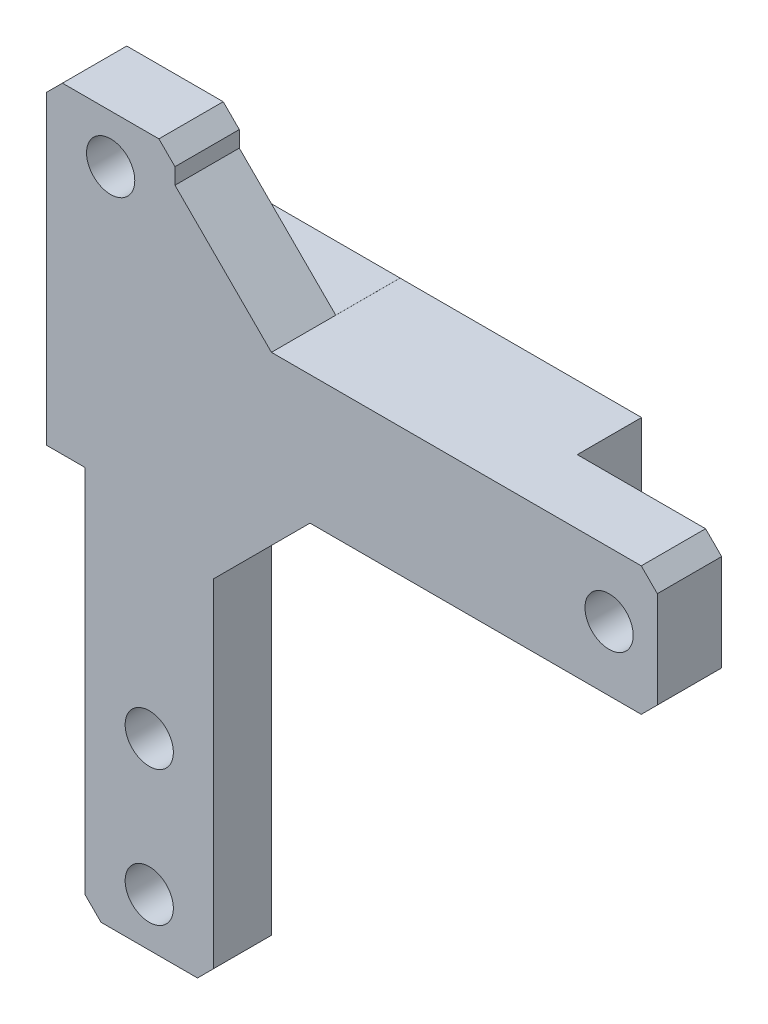
SolidWorks part; units mm, degrees
ref_plane "前视基准面" through (0, 0, 0) normal (0, 0, 1) x (1, 0, 0)
ref_plane "上视基准面" through (0, 0, 0) normal (0, 1, 0) x (1, 0, 0)
ref_plane "右视基准面" through (0, 0, 0) normal (1, 0, 0) x (0, 0, -1)
other "Configuration Table"
sketch "草图1" plane through (0, 0, 0) normal (0, 0, 1) x (1, 0, 0)
  line L0 (-4.3, -2.5) -> (9.5, -2.5)
  line L1 (-5.5, 1.5) -> (9.5, 1.5)
  line L4 (9.5, 1.5) -> (9.5, -2.5)
  line L8 (-9.5, 1.5) -> (-9.5, 5.5)
  line L9 (-9.5, 5.5) -> (-5.5, 5.5)
  line L11 (-5.5, 1.5) -> (-5.5, 5.5)
  line L12 (-9.5, 1.5) -> (-9.5, -4.5)
  line L13 (-8.3, -4.5) -> (-8.3, -16.5)
  line L14 (-8.3, -16.5) -> (-4.3, -16.5)
  line L15 (-4.3, -16.5) -> (-4.3, -2.5)
  line L16 (-9.5, -4.5) -> (-8.3, -4.5)
  circle A0 centre (8, -0.5) radius 0.75
  circle A1 centre (-7.5, 4) radius 0.75
  circle A2 centre (-6.3, -15) radius 0.75
  circle A3 centre (-6.3, -10.8) radius 0.75
  point P0 (0, 0)
  dimension "D16" = 1.5
  dimension "D2" = 6
  dimension "D4" = 2
  dimension "D5" = 1.5
  dimension "D6" = 10
  dimension "D7" = 4
  dimension "D9" = 2
  dimension "D10" = 1.5
  dimension "D11" = 4
  dimension "D12" = 4
  dimension "D13" = 2
  dimension "D14" = 19
  dimension "D17" = 4.2
  dimension "D18" = 1.5
  dimension "D19" = 2
extrude "凸台-拉伸1" add sketch "草图1" along normal blind 4
sketch "草图2" plane through (0, 0, 0) normal (0, 0, 1) x (1, 0, 0)
  line L0 (-8.3, -4.8687) -> (-4.3, -4.8687)
  line L10 (9.5, -2.5) -> (9.5, 1.5)
  line L11 (9.5, 1.5) -> (-5.5, 1.5)
  line L12 (-5.5, 1.5) -> (-5.5, 5.5)
  line L13 (-5.5, 5.5) -> (-9.5, 5.5)
  line L14 (-9.5, 5.5) -> (-9.5, -4.5)
  line L15 (-9.5, -4.5) -> (-8.3, -4.5)
  line L16 (-8.3, -4.5) -> (-8.3, -16.5)
  line L17 (-8.3, -16.5) -> (-4.3, -16.5)
  line L18 (-4.3, -16.5) -> (-4.3, -2.5)
  line L19 (-4.3, -2.5) -> (9.5, -2.5)
  line L26 (-8.3, -4.8687) -> (-8.3, -16.5)
  line L27 (-8.3, -16.5) -> (-4.3, -16.5)
  line L28 (-4.3, -16.5) -> (-4.3, -4.8687)
  circle A0 centre (-6.3, -15) radius 0.75 construction
  circle A1 centre (-6.3, -10.8) radius 0.75 construction
  circle A2 centre (-6.3, -15) radius 0.75
  circle A3 centre (-6.3, -10.8) radius 0.75
  dimension "D2" = 11.6313
  dimension "D1" = 0
extrude "切除-拉伸1" cut sketch "草图2" along normal blind 2.2
sketch "草图3" plane through (0, 0, 0) normal (0, 0, -1) x (-1, 0, 0)
  line L0 (-5.0101, 1.5) -> (-5.0101, -2.5)
  line L1 (5.5, 1.5011) -> (9.5, 1.5011)
  line L10 (-9.5, 1.5) -> (-9.5, -2.5)
  line L11 (-9.5, -2.5) -> (4.3, -2.5)
  line L12 (4.3, -2.5) -> (4.3, -4.8687)
  line L13 (4.3, -4.8687) -> (8.3, -4.8687)
  line L14 (8.3, -4.8687) -> (8.3, -4.5)
  line L15 (8.3, -4.5) -> (9.5, -4.5)
  line L16 (9.5, -4.5) -> (9.5, 5.5)
  line L17 (9.5, 5.5) -> (5.5, 5.5)
  line L18 (5.5, 5.5) -> (5.5, 1.5)
  line L19 (5.5, 1.5) -> (-9.5, 1.5)
  line L20 (-9.5, 1.5) -> (-9.5, -2.5)
  line L21 (-9.5, -2.5) -> (-5.0101, -2.5)
  line L26 (9.5, 1.5011) -> (9.5, 5.5)
  line L27 (9.5, 5.5) -> (5.5, 5.5)
  line L28 (5.5, 5.5) -> (5.5, 1.5011)
  line L29 (-5.0101, 1.5) -> (-9.5, 1.5)
  circle A0 centre (-8, -0.5) radius 0.75 construction
  circle A1 centre (7.5, 4) radius 0.75 construction
  circle A2 centre (-8, -0.5) radius 0.75
  circle A3 centre (7.5, 4) radius 0.75
  dimension "D1" = 0
extrude "切除-拉伸2" cut sketch "草图3" against normal blind 2
chamfer "倒角1" distance 3 angle 45 2 edges at (-4.3, -2.5, 2) (-5.5, 1.5, 2)
chamfer "倒角2" distance 0.5 angle 45 6 edges at (-4.3, -16.5, 3.1) (-8.3, -16.5, 3.1) (-9.5, 5.5, 3) (9.5, -2.5, 3) (9.5, 1.5, 3) (-5.5, 5.5, 3)
